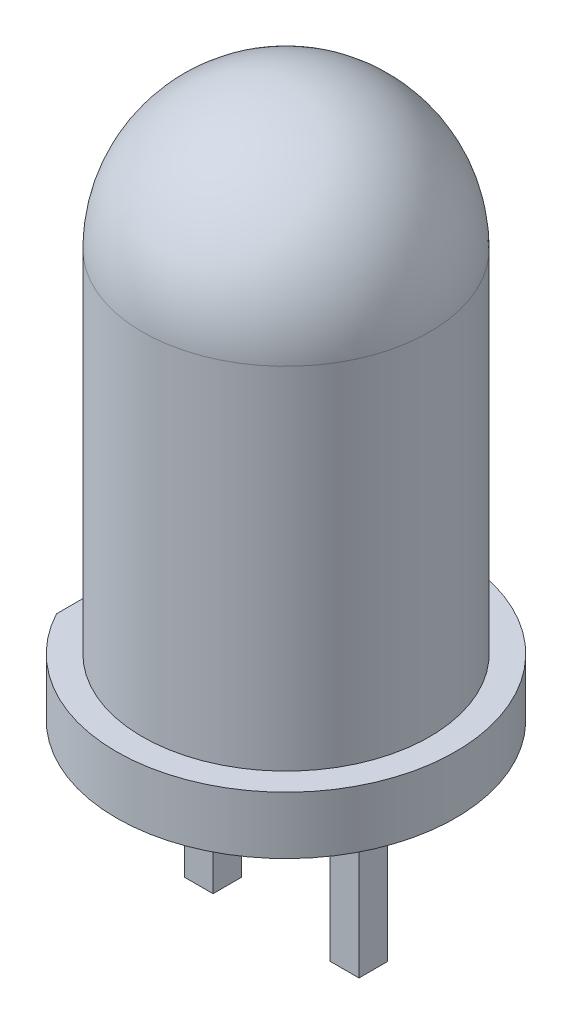
SolidWorks part; units mm, degrees
ref_plane "Front Plane" through (0, 0, 0) normal (0, 0, 1) x (1, 0, 0)
ref_plane "Top Plane" through (0, 0, 0) normal (0, 1, 0) x (1, 0, 0)
ref_plane "Right Plane" through (0, 0, 0) normal (1, 0, 0) x (0, 0, -1)
sketch "Sketch2" plane through (0, 0, 0) normal (1, 0, 0) x (0, 0, -1)
  line L0 (1.02, -1.8) -> (1.52, -1.8)
  line L1 (1.52, -1.8) -> (1.52, 2.09)
  line L2 (1.52, 2.09) -> (1.42, 2.19)
  line L3 (1.42, 2.19) -> (1.42, 3.39)
  line L4 (1.42, 3.39) -> (-0.82, 3.39)
  line L5 (-0.82, 3.39) -> (-0.82, 2.99)
  line L6 (-0.82, 2.99) -> (-0.02, 2.19)
  line L7 (-0.02, 2.19) -> (0.73, 2.19)
  line L8 (0.73, 2.19) -> (1.02, 1.9)
  line L9 (1.02, 1.9) -> (1.02, -1.8)
  line L10 (-1.52, -1.8) -> (-1.02, -1.8)
  line L11 (-1.02, -1.8) -> (-1.02, 1.9)
  line L12 (-1.02, 1.9) -> (-0.73, 2.19)
  line L13 (-0.73, 2.19) -> (-0.47, 2.19)
  line L14 (-0.47, 2.19) -> (-0.47, 2.34)
  line L15 (-0.47, 2.34) -> (-1.12, 2.99)
  line L16 (-1.12, 2.99) -> (-1.12, 3.39)
  line L17 (-1.12, 3.39) -> (-1.42, 3.39)
  line L18 (-1.42, 3.39) -> (-1.42, 2.19)
  line L19 (-1.42, 2.19) -> (-1.52, 2.09)
  line L20 (-1.52, 2.09) -> (-1.52, -1.8)
  line L21 (0, 0) -> (0, 50000) construction
  point P13 (-1.27, -1.8)
  point P24 (1.27, -1.8)
  dimension "D1" = 2.54
  dimension "D2" = 0.5
  dimension "D3" = 3.7
  dimension "D4" = 0.29
  dimension "D5" = 135
  dimension "D6" = 0.1
  dimension "D7" = 0.3
  dimension "D8" = 1.2
  dimension "D9" = 0.75
  dimension "D10" = 0.55
  dimension "D11" = 0.3
  dimension "D12" = 1.8
extrude "Boss-Extrude1" add sketch "Sketch2" along normal mid plane 0.5
sketch "Sketch3" plane through (0, 0, 0) normal (1, 0, 0) x (0, 0, -1)
  line L0 (0, 0) -> (0, 50000) construction
  line L1 (0, 3.39) -> (0.685, 3.39)
  line L2 (1.42, 3.39) -> (-0.82, 3.39) construction
  line L3 (0.6945, 3.3634) -> (0, 2.79)
  line L4 (0, 2.79) -> (0, 3.39)
  line L5 (0, 3.09) -> (0.6, 3.39)
  arc A0 (0.685, 3.39) -> (0.6945, 3.3634) centre (0.685, 3.375) cw
  point P10 (0.7267, 3.39)
  dimension "D1" = 0.015
  dimension "D2" = 0.7
  dimension "D3" = 0.6
  dimension "D4" = 0.3
  dimension "D5" = 0.6
revolve "Revolve1" add sketch "Sketch3" angle 360 about L0 region at (0, 3.29, -0.2) region at (0, 3.119, -0.2707)
revolve "Cut-Revolve1" cut sketch "Sketch3<5>" angle 360 about L0 region at (0, 3.29, -0.2)
sketch "Sketch3<5>" plane through (0, 0, 0) normal (1, 0, 0) x (0, 0, -1) same geometry as "Sketch3"
sketch "Sketch5" plane through (0, 3.39, 0) normal (0, 1, 0) x (1, 0, 0)
  line L1 (-0.15, -0.15) -> (0.15, -0.15)
  line L2 (-0.15, -0.15) -> (-0.15, 0.15)
  line L3 (-0.15, 0.15) -> (0.15, 0.15)
  line L4 (0.15, -0.15) -> (0.15, 0.15)
  line L5 (-0.15, -0.15) -> (0.15, 0.15) construction
  line L6 (-0.15, 0.15) -> (0.15, -0.15) construction
  point P0 (0, 0)
  dimension "D1" = 0.3
extrude "Boss-Extrude2" add sketch "Sketch5" along normal blind 0.1 and the other way up to body separate body
sketch "Sketch6" plane through (0, 0, 0) normal (1, 0, 0) x (0, 0, -1)
  line L0 (0, 0) -> (0, 50000) construction
  line L1 (0, 1.2) -> (2.95, 1.2)
  line L2 (2.95, 1.2) -> (2.95, 2.2)
  line L3 (2.95, 2.2) -> (2.5, 2.2)
  line L4 (2.5, 2.2) -> (2.5, 8.3)
  line L5 (0, 10.8) -> (0, 1.2)
  line L6 (1.02, -1.8) -> (1.52, -1.8) construction
  arc A0 (2.5, 8.3) -> (0, 10.8) centre (0, 8.3) ccw
  dimension "D4" = 2.5
  dimension "D1" = 1
  dimension "D2" = 2.95
  dimension "D3" = 5
  dimension "D5" = 6.1
  dimension "D6" = 3
revolve "Revolve2" add sketch "Sketch6" angle 360 about L0
sketch "Sketch7" plane through (0, 1.2, 0) normal (0, -1, 0) x (1, 0, 0)
  line L0 (-1.3937, -2.6) -> (1.3937, -2.6)
  line L1 (0.25, -1.52) -> (-0.25, -1.52) construction
  circle A0 centre (0, 0) radius 2.95 construction
  arc A2 (-1.3937, -2.6) -> (1.3937, -2.6) centre (0, 0) ccw
  dimension "D1" = 2.6
extrude "Cut-Extrude1" cut sketch "Sketch7" against normal up to surface (1 mm away) up to face at (0, 2.2, -2.5)
move or copy body "Body-Move/Copy1" bodies to move or copy 102 111 106 copy no rotation origin (0, 0, 0) rotation axis (0, 1, 0) rotation angle 90
